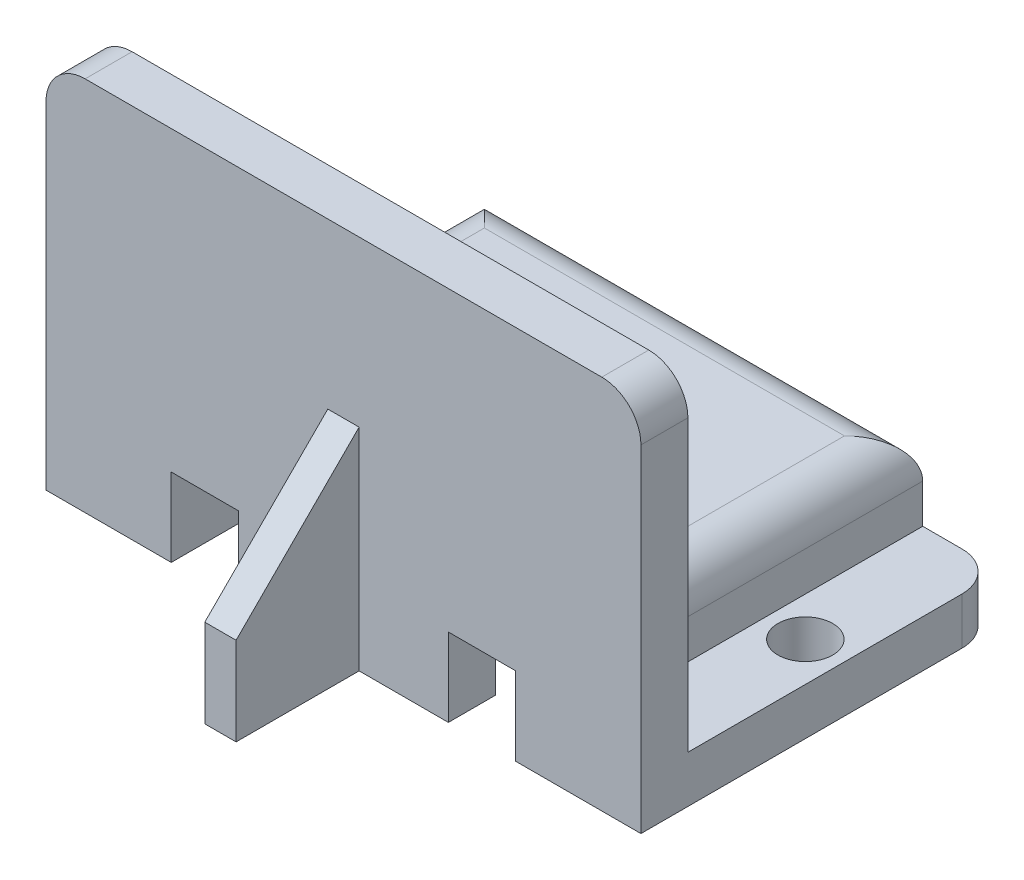
SolidWorks part; units mm, degrees
ref_plane "Front Plane" through (0, 0, 0) normal (0, 0, 1) x (1, 0, 0)
ref_plane "Top Plane" through (0, 0, 0) normal (0, 1, 0) x (1, 0, 0)
ref_plane "Right Plane" through (0, 0, 0) normal (1, 0, 0) x (0, 0, -1)
sketch "Sketch1" plane through (0, 0, 0) normal (1, 0, 0) x (0, 0, -1)
  line L1 (0, 0) -> (3, 0)
  line L2 (0, 0) -> (0, 24)
  line L3 (0, 24) -> (3, 24)
  line L4 (3, 0) -> (3, 24)
  dimension "D1" = 3
  dimension "D2" = 24
extrude "Boss-Extrude1" add sketch "Sketch1" along normal blind 38
sketch "Sketch2" plane through (0, 0, 0) normal (0, 0, 1) x (1, 0, 0)
  line L0 (38, 0) -> (0, 0) construction
  line L1 (18, 0) -> (20, 0)
  line L2 (18, 0) -> (18, 13.4839)
  line L3 (18, 13.4839) -> (20, 13.4839)
  line L4 (20, 0) -> (20, 13.4839)
  line L5 (38, 24) -> (0, 24) construction
  point P6 (19, 24)
  point P7 (19, 13.4839)
  point P10 (0, 0)
  dimension "D1" = 2
extrude "Boss-Extrude2" add sketch "Sketch2" along normal blind 20
chamfer "Chamfer1" distance 20 angle 45 1 edges at (19, 13.4839, 20)
sketch "Sketch3" plane through (0, 0, -3) normal (0, 0, -1) x (-1, 0, 0)
  line L0 (0, 0) -> (0, 24) construction
  line L1 (-38, 3) -> (0, 3)
  line L2 (-38, 3) -> (-38, 0)
  line L3 (-38, 0) -> (0, 0)
  line L4 (0, 3) -> (0, 0)
  line L5 (-38, 0) -> (0, 0) construction
  dimension "D1" = 3
extrude "Boss-Extrude3" add sketch "Sketch3" along normal blind 20
sketch "Sketch4" plane through (0, 0, 0) normal (0, -1, 0) x (1, 0, 0)
  line L0 (38, -23) -> (0, -23) construction
  line L1 (0, -23) -> (0, 0) construction
  line L2 (38, -23) -> (38, 0) construction
  circle A0 centre (2.5, -13) radius 1.75
  circle A1 centre (35.5, -13) radius 1.75
  point P4 (0, 0)
  dimension "D1" = 3.5
  dimension "D2" = 10
  dimension "D3" = 2.5
  dimension "D4" = 2.5
extrude "Cut-Extrude1" cut sketch "Sketch4" against normal through all
sketch "Sketch5" plane through (0, 3, 0) normal (0, 1, 0) x (1, 0, 0)
  line L0 (0, 23) -> (38, 23) construction
  line L1 (5, 23) -> (33, 23)
  line L2 (5, 23) -> (5, 3)
  line L3 (5, 3) -> (33, 3)
  line L4 (33, 23) -> (33, 3)
  line L5 (38, 3) -> (0, 3) construction
  circle A0 centre (2.5, 13) radius 1.75 construction
  circle A1 centre (35.5, 13) radius 1.75 construction
  dimension "D1" = 2.5
  dimension "D2" = 2.5
extrude "Boss-Extrude4" add sketch "Sketch5" along normal blind 5
sketch "Sketch6" plane through (0, 0, 0) normal (0, -1, 0) x (1, 0, 0)
  line L0 (11, -23) -> (27, -23)
  line L2 (27, -23) -> (27, -20)
  line L3 (27, -20) -> (30, -20)
  line L4 (30, -20) -> (30, -3)
  line L5 (30, -3) -> (8, -3)
  line L6 (8, -3) -> (8, -20)
  line L7 (8, -20) -> (11, -20)
  line L8 (11, -20) -> (11, -23)
  line L9 (20, 0) -> (18, 0) construction
  line L10 (33, -3) -> (33, -23) construction
  line L11 (5, -23) -> (5, -3) construction
  line L12 (0, -3) -> (5, -3) construction
  line L14 (38, -23) -> (0, -23) construction
  point P8 (19, 0)
  point P11 (19, -23)
  point P14 (0, 0)
  dimension "D1" = 16
  dimension "D2" = 3
  dimension "D3" = 3
  dimension "D4" = 3
extrude "Cut-Extrude2" cut sketch "Sketch6" against normal offset from surface (5 mm away) 3 up to face at (19, 8, -13)
sketch "Sketch7" plane through (0, 0, -3) normal (0, 0, -1) x (-1, 0, 0)
  line L0 (-30, 0) -> (-8, 0) construction
  line L1 (-30, 0) -> (-25.7004, 0)
  line L2 (-30, 0) -> (-30, 5.0023)
  line L3 (-30, 5.0023) -> (-25.7004, 5.0023)
  line L4 (-25.7004, 0) -> (-25.7004, 5.0023)
  line L5 (-30, 5) -> (-30, 0) construction
  line L6 (-12.2996, 0) -> (-8, 0)
  line L7 (-12.2996, 0) -> (-12.2996, 5.0023)
  line L8 (-12.2996, 5.0023) -> (-8, 5.0023)
  line L9 (-8, 0) -> (-8, 5.0023)
  line L10 (-8, 5) -> (-8, 0) construction
extrude "Cut-Extrude3" cut sketch "Sketch7" against normal blind 15
sketch "Sketch8" plane through (18, 0, 0) normal (-1, 0, 0) x (0, 0, 1)
  line L0 (7.8583, 5.6256) -> (7.8583, 0)
  line L1 (13.4839, 0) -> (0, 13.4839) construction
  line L2 (13.4839, 0) -> (0, 0) construction
  line L3 (7.8583, 0) -> (13.4839, 0)
  line L4 (13.4839, 0) -> (7.8583, 5.6256)
extrude "Cut-Extrude4" cut sketch "Sketch8" against normal blind 15
fillet "Fillet3" radius 2.5 8 edges at (33, 5.5, -3) (5, 5.5, -3) (19, 8, -23) (33, 8, -13) (19, 8, -3) (5, 8, -13) (0, 1.5, -23) (38, 1.5, -23)
sketch "Sketch9" plane through (0, 8, 0) normal (0, 1, 0) x (1, 0, 0)
  line L0 (38, 3) -> (0, 3) construction
  line L1 (11, 3) -> (14, 3)
  line L2 (11, 3) -> (11, 13)
  line L3 (11, 13) -> (14, 13)
  line L4 (14, 3) -> (14, 13)
  line L5 (7.5, 20.5) -> (7.5, 5.5) construction
  line L6 (27, 3) -> (24, 3)
  line L7 (27, 3) -> (27, 13)
  line L8 (27, 13) -> (24, 13)
  line L9 (24, 3) -> (24, 13)
  line L10 (30.5, 5.5) -> (30.5, 20.5) construction
  dimension "D1" = 3
  dimension "D2" = 3.5
  dimension "D3" = 3.5
  dimension "D4" = 10
extrude "Boss-Extrude5" add sketch "Sketch9" along normal blind 7.5
chamfer "Chamfer2" distance 7.5 angle 45 2 edges at (12.5, 15.5, -13) (25.5, 15.5, -13)
fillet "Fillet4" radius 2.5 2 edges at (38, 24, -1.5) (0, 24, -1.5)
